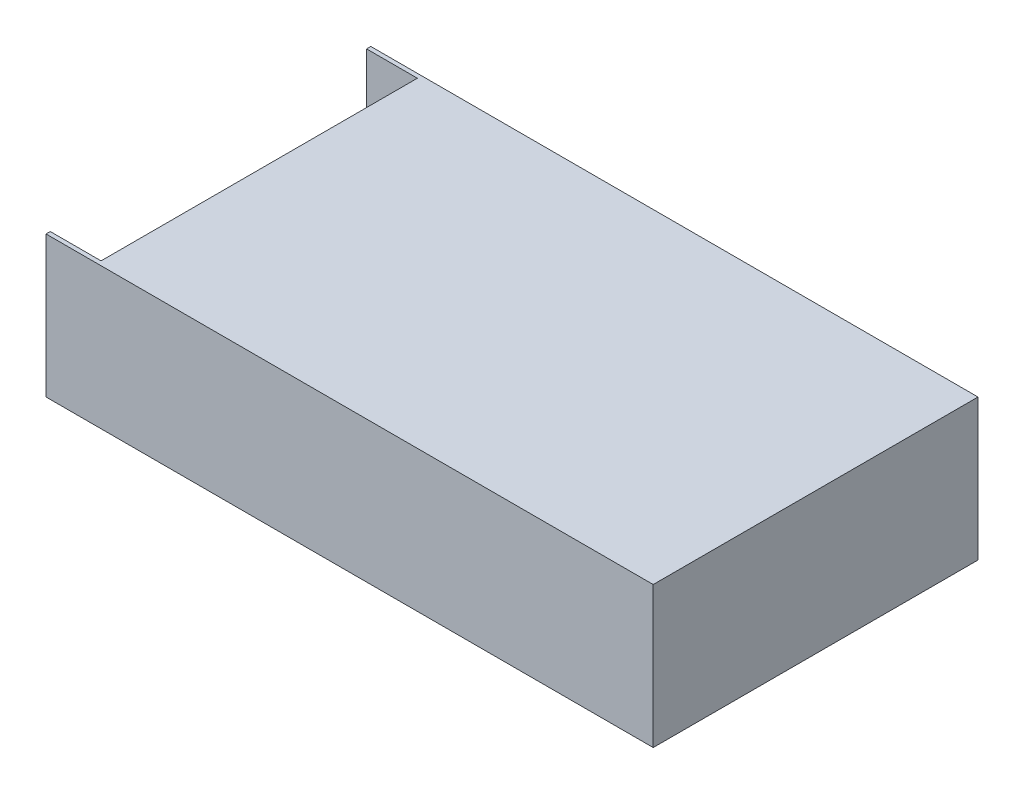
SolidWorks part; units mm, degrees
material "1060 Alloy"
ref_plane "Front" through (0, 0, 0) normal (0, 0, 1) x (1, 0, 0)
ref_plane "Top" through (0, 0, 0) normal (0, 1, 0) x (1, 0, 0)
ref_plane "Right" through (0, 0, 0) normal (1, 0, 0) x (0, 0, -1)
sketch "Sketch1" plane through (0, 0, 0) normal (0, 1, 0) x (1, 0, 0)
  line L1 (-107.5, -57.5) -> (107.5, -57.5)
  line L2 (-107.5, -57.5) -> (-107.5, 57.5)
  line L3 (-107.5, 57.5) -> (107.5, 57.5)
  line L4 (107.5, -57.5) -> (107.5, 57.5)
  line L5 (-107.5, -57.5) -> (107.5, 57.5) construction
  line L6 (-107.5, 57.5) -> (107.5, -57.5) construction
  point P0 (0, 0)
  dimension "D1" = 215
  dimension "D2" = 115
extrude "Boss-Extrude1" add sketch "Sketch1" along normal blind 50
sketch "Sketch2" plane through (0, 50, 0) normal (0, 1, 0) x (1, 0, 0)
  line L0 (-107.5, 57.5) -> (-107.5, -57.5) construction
  line L1 (-107.5, 56) -> (-89.5, 56)
  line L2 (-107.5, 56) -> (-107.5, -56)
  line L3 (-107.5, -56) -> (-89.5, -56)
  line L4 (-89.5, 56) -> (-89.5, -56)
  line L5 (107.5, 57.5) -> (-107.5, 57.5) construction
  line L6 (-107.5, -57.5) -> (107.5, -57.5) construction
  dimension "D1" = 1.5
  dimension "D2" = 1.5
  dimension "D3" = 18
extrude "Cut-Extrude2" cut sketch "Sketch2" against normal blind 25
shell "Shell1" thickness 5 removed face at (0, 0, 0)
